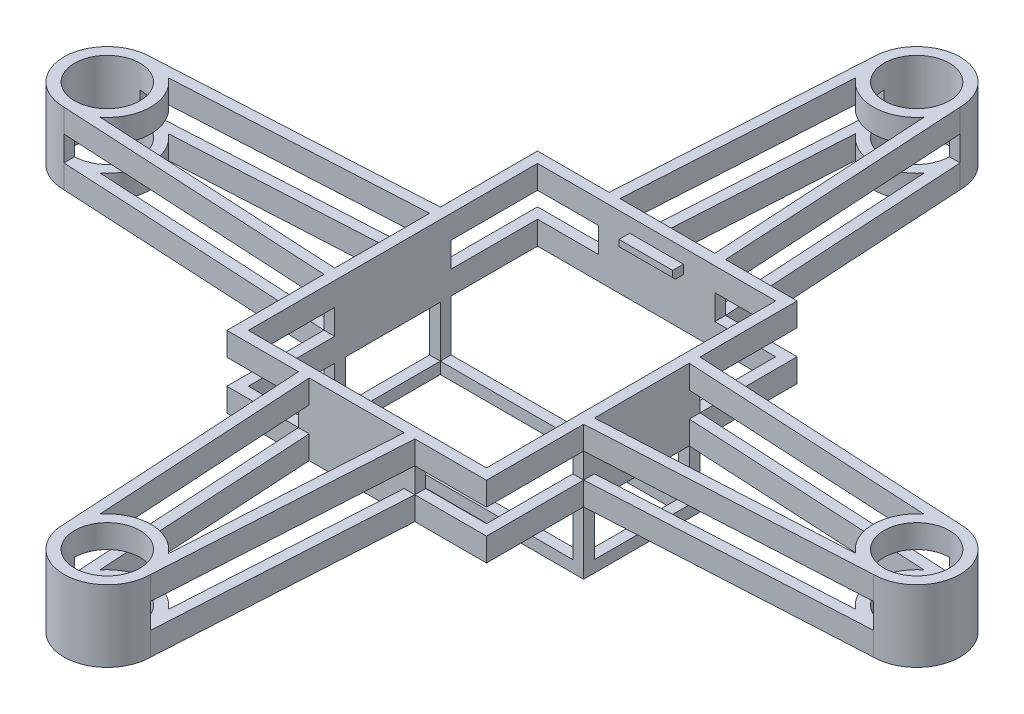
SolidWorks part; units mm, degrees
ref_plane "Front Plane" through (0, 0, 0) normal (0, 0, 1) x (1, 0, 0)
ref_plane "Top Plane" through (0, 0, 0) normal (0, 1, 0) x (1, 0, 0)
ref_plane "Right Plane" through (0, 0, 0) normal (1, 0, 0) x (0, 0, -1)
sketch "Sketch1" plane through (0, 0, 0) normal (0, 1, 0) x (1, 0, 0)
  line L0 (-15.0219, 23.4518) -> (-15.0219, 12.6018)
  line L1 (-13.8219, 22.2518) -> (12.7781, 22.2518)
  line L2 (-13.8219, 22.2518) -> (-13.8219, -10.0482)
  line L3 (-13.8219, -10.0482) -> (12.7781, -10.0482)
  line L4 (12.7781, 22.2518) -> (12.7781, -10.0482)
  line L5 (-15.0219, -11.2482) -> (-7.0219, -11.2482)
  line L6 (13.9781, 23.4518) -> (13.9781, 12.6018)
  line L7 (-15.0219, 23.4518) -> (-7.0219, 23.4518)
  line L8 (-0.5219, 23.4518) -> (-0.5219, 46.4518) construction
  line L9 (-5.3719, 51.3018) -> (-7.0219, 23.4518)
  line L10 (4.3281, 51.3018) -> (5.9781, 23.4518)
  line L11 (-4.3465, 48.3194) -> (-5.824, 23.3808)
  line L12 (3.3027, 48.3194) -> (4.7802, 23.3808)
  line L13 (-15.0219, 6.1018) -> (-40.8719, 6.1018) construction
  line L14 (4.3281, -39.0982) -> (5.9781, -11.2482)
  line L15 (3.3027, -36.1158) -> (4.776, -11.2482)
  line L16 (-5.3719, -39.0982) -> (-7.0219, -11.2482)
  line L17 (-4.3465, -36.1158) -> (-5.8198, -11.2482)
  line L18 (-5.8198, 23.4518) -> (4.776, 23.4518)
  line L19 (-15.0219, 23.4518) -> (13.9781, 23.4518) construction
  line L20 (5.9781, 23.4518) -> (13.9781, 23.4518)
  line L21 (3.1302, 51.2308) -> (4.7802, 23.3808) construction
  line L22 (-4.174, 51.2308) -> (-5.824, 23.3808) construction
  line L23 (5.9781, -11.2482) -> (13.9781, -11.2482)
  line L24 (-15.0219, -11.2482) -> (13.9781, -11.2482) construction
  line L25 (-5.8198, -11.2482) -> (4.776, -11.2482)
  line L26 (-15.0219, 12.6018) -> (-45.7219, 10.9518)
  line L27 (-15.0219, -0.3982) -> (-45.7219, 1.2518)
  line L28 (-15.0219, 11.4001) -> (-42.7204, 9.9114)
  line L29 (-15.0219, 0.8035) -> (-42.7204, 2.2922)
  line L30 (-14.9575, 11.4035) -> (-45.6575, 9.7535) construction
  line L31 (-14.9575, 0.8001) -> (-45.6575, 2.4501) construction
  line L32 (-15.0219, 11.4001) -> (-15.0219, 0.8035)
  line L33 (-15.0219, 23.4518) -> (-15.0219, -11.2482) construction
  line L34 (-15.0219, -0.3982) -> (-15.0219, -11.2482)
  line L35 (-0.5219, 19.2522) -> (-0.5219, -5.3695) construction
  line L36 (13.9781, -0.3982) -> (44.6781, 1.2518)
  line L37 (13.9781, 0.8035) -> (41.6765, 2.2922)
  line L38 (13.9781, 12.6018) -> (44.6781, 10.9518)
  line L39 (13.9781, 11.4001) -> (41.6765, 9.9114)
  line L40 (13.9781, 11.4001) -> (13.9781, 0.8035)
  line L41 (13.9781, 23.4518) -> (13.9781, -11.2482) construction
  line L42 (13.9781, -0.3982) -> (13.9781, -11.2482)
  circle A0 centre (-0.5219, 51.3018) radius 3.65
  arc A1 (-4.3465, 48.3194) -> (3.3027, 48.3194) centre (-0.5219, 51.3018) ccw
  arc A2 (-4.3465, -36.1158) -> (3.3027, -36.1158) centre (-0.5219, -39.0982) cw
  circle A3 centre (-0.5219, -39.0982) radius 3.65
  circle A4 centre (-0.5219, 51.3018) radius 4.85 construction
  arc A5 (4.3281, 51.3018) -> (-5.3719, 51.3018) centre (-0.5219, 51.3018) ccw
  arc A6 (4.3281, -39.0982) -> (-5.3719, -39.0982) centre (-0.5219, -39.0982) cw
  circle A7 centre (-45.7219, 6.1018) radius 3.65
  arc A8 (-45.7219, 10.9518) -> (-45.7219, 1.2518) centre (-45.7219, 6.1018) ccw
  circle A9 centre (-45.7219, 6.1018) radius 4.85 construction
  arc A10 (-42.7204, 2.2922) -> (-42.7204, 9.9114) centre (-45.7219, 6.1018) ccw
  arc A11 (41.6765, 2.2922) -> (41.6765, 9.9114) centre (44.6781, 6.1018) cw
  arc A12 (44.6781, 10.9518) -> (44.6781, 1.2518) centre (44.6781, 6.1018) cw
  circle A13 centre (44.6781, 6.1018) radius 3.65
  point P10 (-0.5219, 51.3018)
  point P15 (-7.0219, 23.4518)
  point P16 (5.9781, 23.4518)
  point P29 (-45.7219, 6.1018)
  point P39 (-0.5219, -39.0982)
  point P44 (-15.0219, 6.1018)
  point P49 (-15.0219, 12.6018)
  point P50 (-15.0219, -0.3982)
  point P76 (44.6781, 6.1018)
  dimension "D5" = 4.85
  dimension "D13" = 1.2
  dimension "D18" = 90.4
  dimension "D1" = 26.6
  dimension "D2" = 32.3
  dimension "D4" = 23
  dimension "D7" = 6.5
  dimension "D8" = 6.5
  dimension "D11" = 25.85
  dimension "D12" = 4.85
  dimension "D14" = 6.5
  dimension "D15" = 6.5
  dimension "D19" = 90.4
  dimension "D3" = 1.2
  dimension "D6" = 1.2
  dimension "D9" = 1.2
  dimension "D10" = 1.2
  dimension "D16" = 1.2
  dimension "D17" = 1.2
extrude "Boss-Extrude1" add sketch "Sketch1" along normal blind 8 contours A12 L38 L6 L20 L10 A5 L9 L7 L0 L26 A8 L27 L34 L5 L16 A6 L14 L23 L42 L36 L29 A10 L28 L32 A3 A2 L17 L25 L15 A0 L1 L4 L3 L2 L11 A1 L12 L18 A7 region at (-11.0219, 0, -23.3102)
sketch "Sketch2" plane through (0, 0, -22.2518) normal (0, 0, 1) x (1, 0, 0)
  line L0 (-13.8219, 8) -> (12.7781, 8) construction
  line L2 (-0.5219, 6.4) -> (-3.5219, 6.4)
  line L3 (-0.5219, 6.4) -> (-0.5219, 5.7)
  line L4 (-0.5219, 5.7) -> (-3.5219, 5.7)
  line L5 (-3.5219, 6.4) -> (-3.5219, 5.7)
  line L6 (-0.5219, 6.4) -> (2.4781, 6.4)
  line L7 (-0.5219, 6.4) -> (-0.5219, 5.7)
  line L8 (-0.5219, 5.7) -> (2.4781, 5.7)
  line L9 (2.4781, 6.4) -> (2.4781, 5.7)
  point P0 (-0.5219, 8)
  point P1 (-0.5219, 6.4)
  dimension "D1" = 1.6
  dimension "D2" = 0.7
  dimension "D3" = 3
  dimension "D4" = 3
extrude "Boss-Extrude2" add sketch "Sketch2" along normal blind 1.2 contours L2 L5 L4 L3 | L9 L6 L3 L8 region at (-2.0219, 6.05, -22.2518) region at (0.9781, 6.05, -22.2518)
sketch "Sketch3" plane through (0, 0, 10.0482) normal (0, 0, -1) x (-1, 0, 0)
  line L0 (13.8219, 8) -> (-12.7781, 8) construction
  line L2 (0.5219, 6.4) -> (-2.4781, 6.4)
  line L3 (0.5219, 6.4) -> (0.5219, 5.7)
  line L4 (0.5219, 5.7) -> (-2.4781, 5.7)
  line L5 (-2.4781, 6.4) -> (-2.4781, 5.7)
  line L6 (0.5219, 6.4) -> (3.5219, 6.4)
  line L7 (0.5219, 6.4) -> (0.5219, 5.7)
  line L8 (0.5219, 5.7) -> (3.5219, 5.7)
  line L9 (3.5219, 6.4) -> (3.5219, 5.7)
  point P0 (0.5219, 8)
  point P1 (0.5219, 6.4)
  dimension "D1" = 1.6
  dimension "D2" = 0.7
  dimension "D3" = 3
  dimension "D4" = 3
extrude "Boss-Extrude3" add sketch "Sketch3" along normal blind 1.2 contours L2 L5 L4 L3 | L9 L6 L3 L8 region at (0.9781, 6.05, 10.0482) region at (-2.0219, 6.05, 10.0482)
chamfer "Chamfer1" distance 1.2 angle 45 2 edges at (-0.5219, 5.7, -22.2518) (-0.5219, 5.7, 10.0482)
sketch "Sketch4" plane through (0, 0, -23.4518) normal (0, 0, -1) x (-1, 0, 0)
  line L0 (-49.5281, 4) -> (52.6578, 4) construction
  line L1 (-49.5281, 8) -> (-49.5281, 0) construction
  line L3 (52.6578, 4) -> (-53.577, 4)
  line L4 (52.6578, 4) -> (52.6578, 5.4)
  line L5 (52.6578, 5.4) -> (-53.577, 5.4)
  line L6 (-53.577, 4) -> (-53.577, 5.4)
  line L7 (-53.577, 4) -> (52.6578, 4)
  line L8 (-53.577, 4) -> (-53.577, 2.6)
  line L9 (-53.577, 2.6) -> (52.6578, 2.6)
  line L10 (52.6578, 4) -> (52.6578, 2.6)
  line M4 (5.8198, 0) -> (5.8198, 8)
  line M6 (-4.776, 8) -> (-4.776, 0)
  dimension "D1" = 1.4
  dimension "D2" = 1.4
extrude "Cut-Extrude1" cut sketch "Sketch4" against normal through all both and the other way through all contours L8 L9 L3 L7 M6 | L6 L7 L3 L5 M6 | L5 L3 M4 M6 | L9 L3 M6 M4 | L10 L3 L9 M4 | L4 L5 L3 M4 region at (-29.2388, 3.3, -23.4518) region at (-29.2388, 4.7, -23.4518) region at (-0.5219, 3.3, -23.4518) region at (-0.5219, 4.7, -23.4518) region at (29.1765, 3.3, -23.4518) region at (29.1765, 4.7, -23.4518)
sketch "Sketch5" plane through (0, 8, 0) normal (0, 1, 0) x (1, 0, 0)
  line L0 (-13.8219, 22.2518) -> (12.7781, 22.2518) construction
  line L1 (-7.0219, 23.4518) -> (5.9781, 23.4518)
  line L2 (-7.0219, 23.4518) -> (-7.0219, 22.2518)
  line L3 (-7.0219, 22.2518) -> (5.9781, 22.2518)
  line L4 (5.9781, 23.4518) -> (5.9781, 22.2518)
  line L5 (-13.8219, -10.0482) -> (12.7781, -10.0482) construction
  line L6 (-7.0219, -11.2482) -> (5.9781, -11.2482)
  line L7 (-7.0219, -11.2482) -> (-7.0219, -10.0482)
  line L8 (-7.0219, -10.0482) -> (5.9781, -10.0482)
  line L9 (5.9781, -11.2482) -> (5.9781, -10.0482)
  line L10 (-13.8219, 22.2518) -> (-13.8219, -10.0482) construction
  line L11 (-15.0219, 12.6018) -> (-13.8219, 12.6018)
  line L12 (-15.0219, 12.6018) -> (-15.0219, -0.3982)
  line L13 (-15.0219, -0.3982) -> (-13.8219, -0.3982)
  line L14 (-13.8219, 12.6018) -> (-13.8219, -0.3982)
  line L15 (12.7781, 22.2518) -> (12.7781, -10.0482) construction
  line L16 (13.9781, 12.6018) -> (12.7781, 12.6018)
  line L17 (13.9781, 12.6018) -> (13.9781, -0.3982)
  line L18 (13.9781, -0.3982) -> (12.7781, -0.3982)
  line L19 (12.7781, 12.6018) -> (12.7781, -0.3982)
extrude "Boss-Extrude4" add sketch "Sketch5" against normal through all
sketch "Sketch6" plane through (0, 8, 0) normal (0, 1, 0) x (1, 0, 0)
  line L0 (-5.3719, 51.3018) -> (-4.1719, 51.3018)
  line L1 (3.1281, 51.3018) -> (4.3281, 51.3018)
  line L2 (-10.3547, 6.1018) -> (10.8442, 6.1018) construction
  line L3 (3.1281, -39.0982) -> (4.3281, -39.0982)
  line L4 (-5.3719, -39.0982) -> (-4.1719, -39.0982)
  line L5 (44.6781, 9.7518) -> (44.6781, 10.9518)
  line L6 (44.6781, 1.2518) -> (44.6781, 2.4518)
  line L7 (-0.5219, 19.9558) -> (-0.5219, -2.6234) construction
  line L8 (-45.7219, 1.2518) -> (-45.7219, 2.4518)
  line L9 (-45.7219, 9.7518) -> (-45.7219, 10.9518)
  arc A0 (4.3281, 51.3018) -> (-5.3719, 51.3018) centre (-0.5219, 51.3018) ccw
  arc A1 (3.1281, 51.3018) -> (-4.1719, 51.3018) centre (-0.5219, 51.3018) ccw
  arc A2 (3.1281, -39.0982) -> (-4.1719, -39.0982) centre (-0.5219, -39.0982) cw
  arc A3 (4.3281, -39.0982) -> (-5.3719, -39.0982) centre (-0.5219, -39.0982) cw
  arc A4 (44.6781, 9.7518) -> (44.6781, 2.4518) centre (44.6781, 6.1018) cw
  arc A5 (44.6781, 10.9518) -> (44.6781, 1.2518) centre (44.6781, 6.1018) cw
  arc A6 (-45.7219, 10.9518) -> (-45.7219, 1.2518) centre (-45.7219, 6.1018) ccw
  arc A7 (-45.7219, 9.7518) -> (-45.7219, 2.4518) centre (-45.7219, 6.1018) ccw
  dimension "D2" = 7.3
extrude "Boss-Extrude5" add sketch "Sketch6" against normal through all
sketch "Sketch7" plane through (0, 0, 0) normal (0, -1, 0) x (1, 0, 0)
  line L0 (-13.8219, -22.2518) -> (-13.8219, 10.0482) construction
  line L1 (-15.0219, 0.3982) -> (-13.8219, 0.3982)
  line L2 (-15.0219, 0.3982) -> (-15.0219, -0.8039)
  line L3 (-15.0219, -0.8039) -> (-13.8219, -0.8039)
  line L4 (-13.8219, 0.3982) -> (-13.8219, -0.8039)
  line L5 (12.7781, -22.2518) -> (12.7781, 10.0482) construction
  line L6 (-15.0219, -11.4001) -> (-13.8219, -11.4001)
  line L7 (-15.0219, -11.4001) -> (-15.0219, -12.6018)
  line L8 (-15.0219, -12.6018) -> (-13.8219, -12.6018)
  line L9 (-13.8219, -11.4001) -> (-13.8219, -12.6018)
  line L10 (13.9781, 0.3982) -> (12.7781, 0.3982)
  line L11 (13.9781, 0.3982) -> (13.9781, -0.8039)
  line L12 (13.9781, -0.8039) -> (12.7781, -0.8039)
  line L13 (12.7781, 0.3982) -> (12.7781, -0.8039)
  line L15 (13.9781, -11.4001) -> (12.7781, -11.4001)
  line L16 (13.9781, -11.4001) -> (13.9781, -12.6018)
  line L17 (13.9781, -12.6018) -> (12.7781, -12.6018)
  line L18 (12.7781, -11.4001) -> (12.7781, -12.6018)
extrude "Boss-Extrude6" add sketch "Sketch7" along normal blind 7
sketch "Sketch8" plane through (-13.8219, 0, 0) normal (1, 0, 0) x (0, 0, -1)
  line L0 (0.8039, -7) -> (0.8039, 0) construction
  line L1 (-0.3982, -7) -> (0.8039, -7)
  line L2 (-0.3982, -7) -> (-0.3982, -5.7)
  line L3 (-0.3982, -5.7) -> (0.8039, -5.7)
  line L4 (0.8039, -7) -> (0.8039, -5.7)
  line L5 (11.4001, -7) -> (11.4001, 0) construction
  line L6 (11.4001, -5.7) -> (12.6018, -5.7)
  line L7 (11.4001, -5.7) -> (11.4001, -7)
  line L8 (11.4001, -7) -> (12.6018, -7)
  line L9 (12.6018, -5.7) -> (12.6018, -7)
  dimension "D1" = 1.3
extrude "Boss-Extrude7" add sketch "Sketch8" along normal up to surface (26.6 mm away) up to face at (12.7781, 1, -6.1018)
sketch "Sketch9" plane through (0, 0, -12.6018) normal (0, 0, -1) x (-1, 0, 0)
  line L1 (-13.9781, -7) -> (-12.7781, -7)
  line L2 (-13.9781, -7) -> (-13.9781, -5.7)
  line L3 (-13.9781, -5.7) -> (-12.7781, -5.7)
  line L4 (-12.7781, -7) -> (-12.7781, -5.7)
  line L5 (15.0219, -7) -> (13.8219, -7)
  line L6 (15.0219, -7) -> (15.0219, -5.7)
  line L7 (15.0219, -5.7) -> (13.8219, -5.7)
  line L8 (13.8219, -7) -> (13.8219, -5.7)
extrude "Boss-Extrude8" add sketch "Sketch9" against normal up to surface (11.7979 mm away) up to face at (-0.5219, -3.175, -0.8039)
